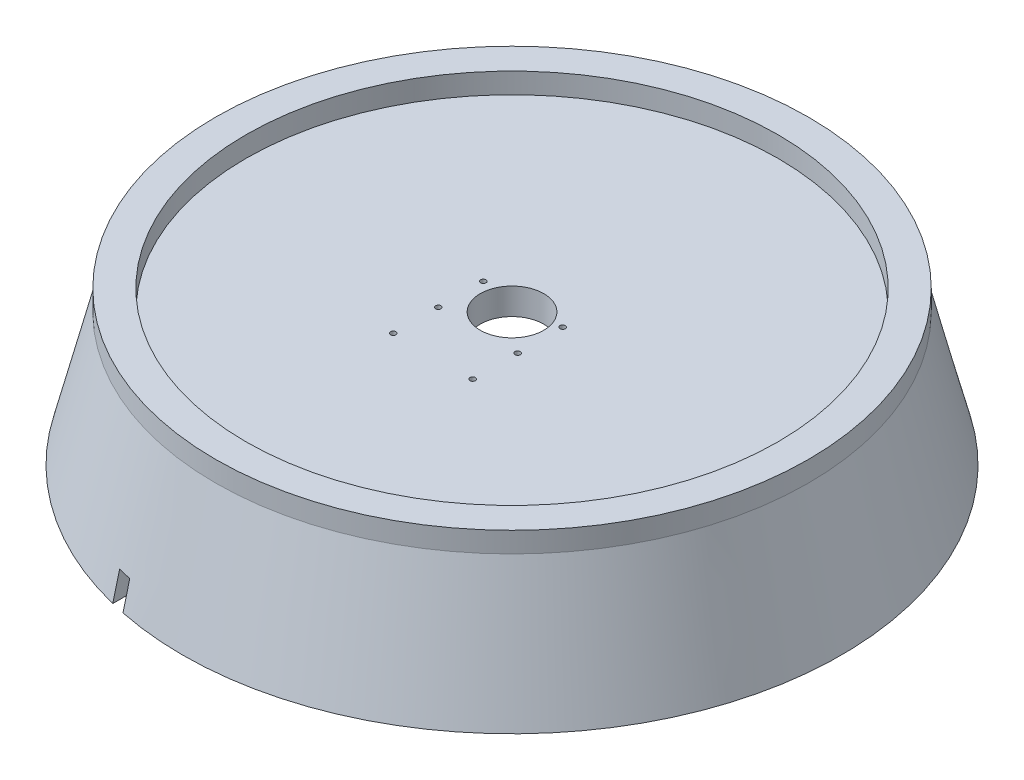
SolidWorks part; units mm, degrees
material "ABS"
ref_plane "Front Plane" through (0, 0, 0) normal (0, 0, 1) x (1, 0, 0)
ref_plane "Top Plane" through (0, 0, 0) normal (0, 1, 0) x (1, 0, 0)
ref_plane "Right Plane" through (0, 0, 0) normal (1, 0, 0) x (0, 0, -1)
sketch "Sketch4" plane through (0, 0, 0) normal (0, 0, 1) x (1, 0, 0)
  line L1 (12, 0) -> (12, 50)
  line L2 (12, 50) -> (112, 50)
  line L3 (112, 50) -> (124.5, 0)
  line L4 (12, 40) -> (104.1922, 40)
  line L5 (104.1922, 40) -> (104.1922, 0)
  line L6 (0, 0) -> (0, 40)
  line L7 (104.1922, 0) -> (124.5, 0)
  dimension "D1" = 12
  dimension "D2" = 100
  dimension "D3" = 50
  dimension "D4" = 10
  dimension "D5" = 90
  dimension "D6" = 10
  dimension "D7" = 112.5
ref_axis "Axis4" through (0, 0, 0) along (0, 1, 0)
revolve "Revolve1" add sketch "Sketch4" angle 360 about L6 region at (13.2311, 45, 0)
sketch "Sketch10" plane through (0, 40, 0) normal (0, -1, 0) x (1, 0, 0)
  line L1 (18.25, -12) -> (-18.25, -12)
  line L2 (18.25, -12) -> (18.25, 38.5)
  line L3 (18.25, 38.5) -> (-18.25, 38.5)
  line L4 (-18.25, -12) -> (-18.25, 38.5)
  line L5 (18.25, -12) -> (-18.25, 38.5) construction
  line L6 (18.25, 38.5) -> (-18.25, -12) construction
  circle A0 centre (-15.45, 29.4) radius 1.025
  circle A1 centre (14.55, 29.4) radius 1.025
  circle A2 centre (14.55, 12.4) radius 1.025
  circle A3 centre (14.55, -4.6) radius 1.025
  circle A4 centre (-15.45, 12.4) radius 1.025
  circle A5 centre (-15.45, -4.6) radius 1.025
  point P0 (0, 13.25)
  dimension "D3" = 2.05
  dimension "D1" = 36.5
  dimension "D2" = 50.5
  dimension "D4" = 9.1
  dimension "D5" = 2.8
  dimension "D8" = 17
  dimension "D9" = 30
  dimension "D10" = 12
  dimension "D6" = 2
  dimension "D7" = 3
extrude "Cut-Extrude2" cut sketch "Sketch10" against normal up to surface (10 mm away) contours A2 | A4 | A0 | A1 | A3 | A5 region at (14.55, 40, 12.4) up to face at (0, 50, -112)
sketch "Sketch11" plane through (0, 50, 0) normal (0, 1, 0) x (1, 0, 0)
  circle A0 centre (0, 0) radius 100.5
  circle A1 centre (0, 0) radius 112
  dimension "D1" = 201
  dimension "D2" = 224
extrude "Boss-Extrude1" add sketch "Sketch11" along normal blind 7.75
sketch "Sketch13" plane through (0, 0, 0) normal (0, 0, 1) x (1, 0, 0)
  line L0 (104.1922, 0) -> (84.1922, 0)
  line L1 (-104.1922, 0) -> (104.1922, 0) construction
  line L2 (84.1922, 0) -> (84.1922, 10)
  line L3 (-104.1922, 40) -> (104.1922, 40) construction
  line L4 (54.1922, 40) -> (15.575, 40)
  line L5 (54.1922, 40) -> (104.1922, 40)
  line L6 (104.1922, 40) -> (104.1922, 0)
  arc A0 (84.1922, 10) -> (54.1922, 40) centre (54.1922, 10) ccw
  point P9 (104.1922, 40)
  point P16 (84.1922, 40)
  dimension "D1" = 20
  dimension "D2" = 30
extrude "Boss-Extrude2" add sketch "Sketch13" along normal mid plane 40 contours A0 L2 L0 L6 L5 region at (90.9443, 22.5863, 0)
pattern_circular "CirPattern1" count 5 over 360 about axis through (0, 40, 0) along (0, -1, 0) of "Boss-Extrude2"
ref_plane "Plane1" through (0, 0, 125) normal (0, 0, 1) x (1, 0, 0)
sketch "Sketch14" plane through (0, 0, 125) normal (0, 0, 1) x (1, 0, 0)
  line L0 (-124.5, 0) -> (124.5, 0) construction
  line L1 (-25, 0) -> (-30, 0)
  line L2 (-25, 0) -> (-25, 10)
  line L3 (-25, 10) -> (-30, 10)
  line L4 (-30, 0) -> (-30, 10)
  line L5 (0, 0) -> (0, 40) construction
  dimension "D1" = 5
  dimension "D2" = 10
  dimension "D3" = 25
extrude "Cut-Extrude3" cut sketch "Sketch14" against normal through all both
